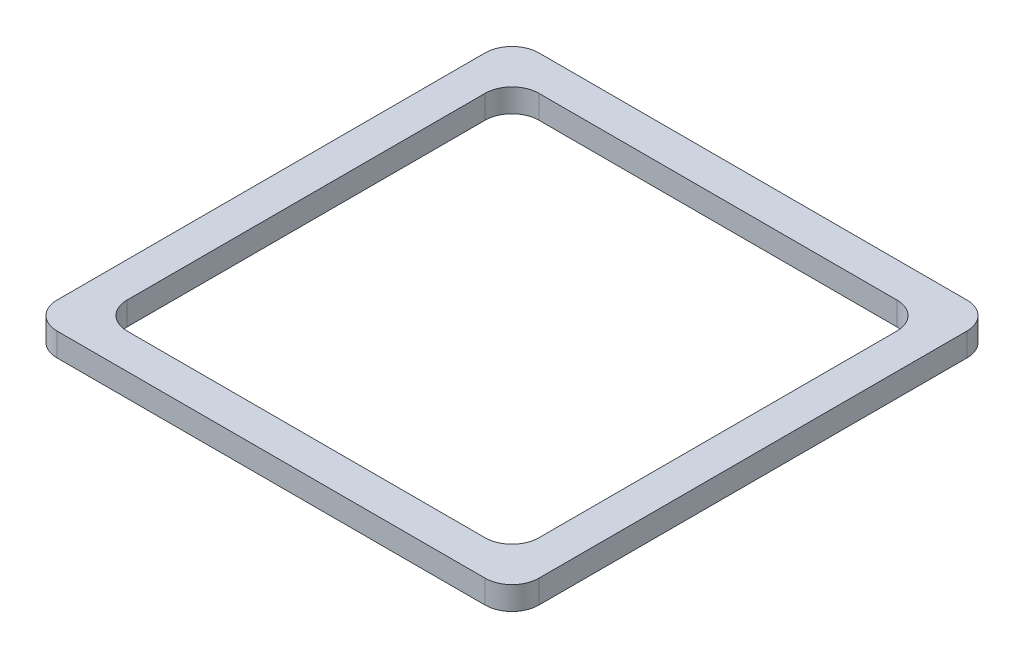
SolidWorks part; units mm, degrees
ref_plane "Front Plane" through (0, 0, 0) normal (0, 0, 1) x (1, 0, 0)
ref_plane "Top Plane" through (0, 0, 0) normal (0, 1, 0) x (1, 0, 0)
ref_plane "Right Plane" through (0, 0, 0) normal (1, 0, 0) x (0, 0, -1)
sketch "Sketch1" plane through (0, 0, 0) normal (0, 1, 0) x (1, 0, 0)
  line L0 (-8.825, -8.825) -> (-7.675, -8.825) construction
  line L1 (-10.325, -10.325) -> (10.325, -10.325)
  line L2 (-10.325, -10.325) -> (-10.325, 10.325)
  line L3 (-10.325, 10.325) -> (10.325, 10.325)
  line L4 (10.325, -10.325) -> (10.325, 10.325)
  line L5 (-10.325, -10.325) -> (10.325, 10.325) construction
  line L6 (-10.325, 10.325) -> (10.325, -10.325) construction
  line L7 (-8.825, -8.825) -> (8.825, -8.825)
  line L8 (-8.825, -8.825) -> (-8.825, 8.825)
  line L9 (-8.825, 8.825) -> (8.825, 8.825)
  line L10 (8.825, -8.825) -> (8.825, 8.825)
  line L11 (-8.825, -8.825) -> (8.825, 8.825) construction
  line L12 (-8.825, 8.825) -> (8.825, -8.825) construction
  line L13 (-8.825, -8.825) -> (-8.825, -7.675) construction
  arc A0 (-7.675, -8.825) -> (-8.825, -7.675) centre (-7.675, -7.675) cw
  arc A1 (-8.825, 7.675) -> (-7.675, 8.825) centre (-7.675, 7.675) cw
  arc A2 (7.675, 8.825) -> (8.825, 7.675) centre (7.675, 7.675) cw
  arc A3 (8.825, -7.675) -> (7.675, -8.825) centre (7.675, -7.675) cw
  point P0 (0, 0)
  point P6 (0, 0)
  point P26 (0, 0)
  dimension "D1" = 20.65
  dimension "D3" = 17.65
  dimension "D4" = 1.15
  dimension "D5" = 1.15
  dimension "D6" = 4
extrude "Boss-Extrude1" add sketch "Sketch1" along normal blind 1 contours L1 L4 L3 L2 L10 L7 L8 L9 | L7 A0 L8 | L8 A1 L9 | L9 A2 L10 | L10 A3 L7 region at (-10.033, 0, 0) region at (-8.5681, 0, 8.5681) region at (8.5681, 0, 8.5681) region at (-8.5681, 0, -8.5681) region at (8.5681, 0, -8.5681)
ref_axis "Axis1" through (0, 0, 0) along (0, 1, 0)
fillet "Fillet1" radius 1.15 4 edges at (-10.325, 0.5, -10.325) (-10.325, 0.5, 10.325) (10.325, 0.5, 10.325) (10.325, 0.5, -10.325)
